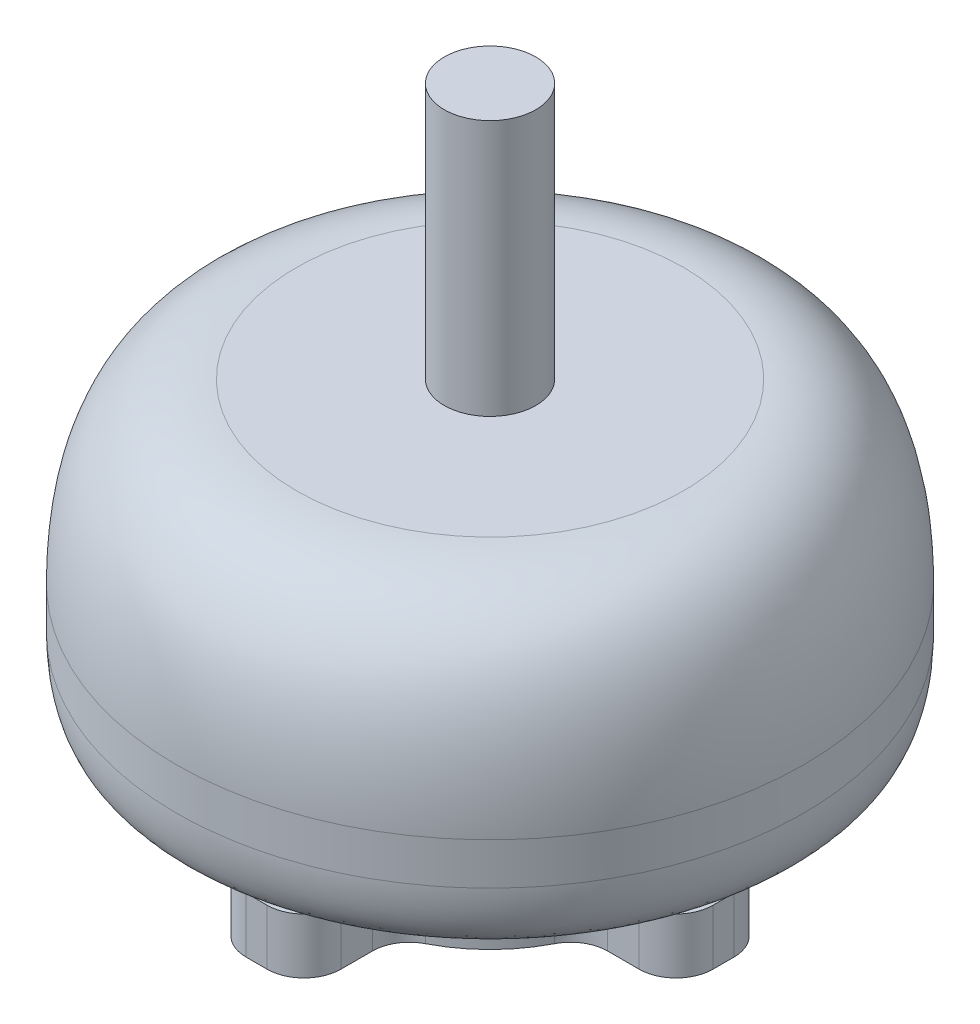
SolidWorks part; units mm, degrees
ref_plane "Front Plane" through (0, 0, 0) normal (0, 0, 1) x (1, 0, 0)
ref_plane "Top Plane" through (0, 0, 0) normal (0, 1, 0) x (1, 0, 0)
ref_plane "Right Plane" through (0, 0, 0) normal (1, 0, 0) x (0, 0, -1)
sketch "Sketch1" plane through (0, 0, 0) normal (0, 1, 0) x (1, 0, 0)
  line L0 (0, 0) -> (0, 12.63) construction
  line L1 (-2.565, 7.6093) -> (-2.565, 12.63)
  line L2 (-2.565, 12.63) -> (2.565, 12.63)
  line L3 (2.565, 12.63) -> (2.565, 7.6093)
  line L4 (0, 8.03) -> (0, 6.26) construction
  circle A0 centre (0, 0) radius 6.26
  circle A1 centre (0, 0) radius 8.03
  circle A2 centre (0, 9.57) radius 1.21
  circle A3 centre (0, 0) radius 7.145
  circle A4 centre (0, 0) radius 16.97
  circle A5 centre (0, 0) radius 2.475
  point P14 (0, 7.145)
  dimension "D1" = 12.52
  dimension "D2" = 16.06
  dimension "D3" = 2.42
  dimension "D4" = 1.85
  dimension "D7" = 33.94
  dimension "D8" = 4.95
  dimension "D5" = 5.13
  dimension "D6" = 8.36
extrude "Boss-Extrude1" add sketch "Sketch1" along normal blind 3 contours A0 A1 | A3 | A0 region at (0, 0, -7.8029)
extrude "Boss-Extrude3" add sketch "Sketch1<4>" along normal blind 3 contours A1 L3 L2 L1 A2 region at (-2.4932, 0, -10.1197)
sketch "Sketch1<4>" plane through (0, 0, 0) normal (0, 1, 0) x (1, 0, 0) same geometry as "Sketch1"
fillet "Fillet1" radius 2 4 edges at (2.565, 1.5, -12.63) (-2.565, 1.5, -12.63) (-2.565, 1.5, -7.6093) (2.565, 1.5, -7.6093)
pattern_circular "CirPattern1" count 4 over 360 about axis through (0, 3, 0) along (0, -1, 0) of "Fillet1", "Boss-Extrude3"
extrude "Boss-Extrude4" add sketch "Sketch1<5>" along normal blind 3.2 from surface contours A3 A0 | A0 A5 | A5 region at (-6.0829, 0, 0) region at (-6.9429, 0, 0) region at (0, 0, 0) starting at face at (0, 3, 0)
sketch "Sketch1<5>" plane through (0, 0, 0) normal (0, 1, 0) x (1, 0, 0) same geometry as "Sketch1"
extrude "Boss-Extrude5" add sketch "Sketch1<6>" along normal blind 14.85 from surface contours A4 starting at face at (0, 6.2, 7.145)
sketch "Sketch1<6>" plane through (0, 0, 0) normal (0, 1, 0) x (1, 0, 0) same geometry as "Sketch1"
extrude "Boss-Extrude6" add sketch "Sketch1<7>" along normal blind 13.86 from surface contours A5 region at (0, 0, 0) starting at face at (0, 21.05, 16.97)
sketch "Sketch1<7>" plane through (0, 0, 0) normal (0, 1, 0) x (1, 0, 0) same geometry as "Sketch1"
sketch "Sketch2" plane through (0, 0, 0) normal (0, 0, 1) x (1, 0, 0)
  line L0 (-16.97, 6.2) -> (16.97, 6.2) construction
  line L1 (16.97, 21.05) -> (-16.97, 21.05) construction
  line L2 (-16.97, 6.2) -> (16.97, 6.2)
  line L3 (16.97, 21.05) -> (-16.97, 21.05)
  line L4 (16.97, 6.2) -> (16.97, 21.05) construction
  line L5 (16.97, 6.2) -> (16.97, 21.05)
  line L6 (15.264, 21.05) -> (10.6654, 21.05) construction
  line L7 (0, 21.05) -> (0, 6.2) construction
  spline S0 degree 3 poles (10.47, 21.05) (18.5455, 21.05) (17.0569, 9.1675) (16.47, 6.2) knots 0 0 0 0 1 1 1 1
  point P9 (-1.5945, 21.05)
  point P12 (0, 0)
  dimension "D1" = 0.5
  dimension "D2" = 6.5
revolve "Cut-Revolve2" cut sketch "Sketch2" angle 360 about L7 region at (15.6549, 19.0967, 0)
fillet "Fillet3" radius 1 1 edges at (0, 6.2, 16.97) second distance 3 first distance on face at (0, 6.2, 7.145)
